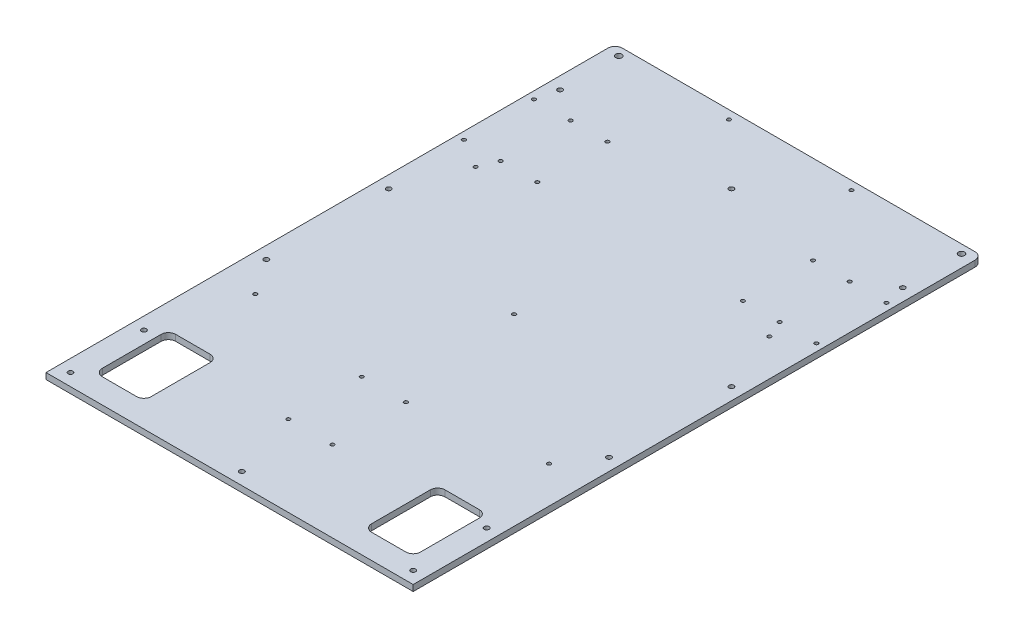
SolidWorks part; units mm, degrees
ref_plane "Front Plane" through (0, 0, 0) normal (0, 0, 1) x (1, 0, 0)
ref_plane "Top Plane" through (0, 0, 0) normal (0, 1, 0) x (1, 0, 0)
ref_plane "Right Plane" through (0, 0, 0) normal (1, 0, 0) x (0, 0, -1)
sketch "Sketch1" plane through (0, 0, 0) normal (0, 1, 0) x (1, 0, 0)
  line L0 (0, -210) -> (0, 210) construction
  line L1 (-150, -210) -> (150, -210)
  line L2 (-150, -210) -> (-150, 210)
  line L3 (-150, 210) -> (150, 210) construction
  line L4 (150, -210) -> (150, 210)
  line L5 (-150, 0) -> (150, 0) construction
  line L6 (-250, 154.9706) -> (0, 404.9706) construction
  line L7 (0, 404.9706) -> (250, 154.9706) construction
  line L8 (-130, -190) -> (-90, -190)
  line L9 (-130, -190) -> (-130, -130)
  line L10 (-130, -130) -> (-90, -130)
  line L11 (-90, -190) -> (-90, -130)
  line L12 (-130, -190) -> (-90, -130) construction
  line L13 (-130, -130) -> (-90, -190) construction
  line L14 (-250, 260) -> (250, 260) construction
  line L15 (-250, 260) -> (-250, -240) construction
  line L16 (-250, -240) -> (250, -240) construction
  line L17 (250, 260) -> (250, -240) construction
  line L18 (-188, 200) -> (-140, 200) construction
  line L19 (-165, 186) -> (-155, 186) construction
  line L20 (-165, 186) -> (-165, 122) construction
  line L21 (-165, 122) -> (-155, 122) construction
  line L22 (-155, 186) -> (-155, 122) construction
  line L23 (-140, 200) -> (-140, 248) construction
  line L24 (-140, 210) -> (-140, -210) construction
  line L25 (-150, -200) -> (150, -200) construction
  line L26 (-130, -160) -> (-90, -160) construction
  line L27 (-110, -190) -> (-110, -130) construction
  line L28 (-140, 248) -> (150, 248) construction
  line L29 (-140, 200) -> (0, 200) construction
  line L30 (0, 182.625) -> (-150, 182.625) construction
  line L31 (130, -190) -> (90, -190)
  line L32 (130, -190) -> (130, -130)
  line L33 (130, -130) -> (90, -130)
  line L34 (90, -190) -> (90, -130)
  line L35 (-200, -205) -> (-200, 200) construction
  line L36 (-155, 154) -> (0, 154) construction
  line L37 (-150, 190) -> (0, 190) construction
  line L38 (-150, 118) -> (0, 118) construction
  line L39 (-150, 210) -> (-150, 255)
  line L40 (-150, 255) -> (150, 255)
  line L41 (150, 255) -> (150, 210)
  circle A0 centre (-140, 248) radius 12 construction
  circle A1 centre (-188, 200) radius 12 construction
  circle A2 centre (-188, -205) radius 12 construction
  circle A3 centre (0, -200) radius 2
  circle A4 centre (-140, -200) radius 2
  circle A15 centre (-140, -40) radius 2
  circle A16 centre (-140, 60) radius 2
  circle A30 centre (140, -200) radius 2
  circle A31 centre (-114, 182.625) radius 1.5
  circle A32 centre (-144, 182.625) radius 1.5
  circle A33 centre (-84, 182.625) radius 1.5
  circle A34 centre (-84, 125.375) radius 1.5
  circle A35 centre (-114, 125.375) radius 1.5
  circle A36 centre (-144, 125.375) radius 1.5
  circle A37 centre (-140, -140) radius 2
  circle A38 centre (-140, 248) radius 2.5
  circle A39 centre (-50, 248) radius 1.5
  circle A40 centre (140, -140) radius 2
  circle A41 centre (140, -200) radius 2
  circle A42 centre (140, 60) radius 2
  circle A43 centre (140, -40) radius 2
  circle A44 centre (144, 125.375) radius 1.5
  circle A45 centre (114, 125.375) radius 1.5
  circle A46 centre (84, 125.375) radius 1.5
  circle A47 centre (84, 182.625) radius 1.5
  circle A48 centre (144, 182.625) radius 1.5
  circle A49 centre (114, 182.625) radius 1.5
  circle A51 centre (50, 248) radius 1.5
  circle A52 centre (140, 248) radius 2.5
  circle A53 centre (-140, 200) radius 2
  circle A54 centre (0, 200) radius 2
  circle A55 centre (140, 200) radius 2
  point P0 (0, 0)
  point P8 (-110, -160)
  point P17 (0, -240)
  dimension "D15" = 24
  dimension "D16" = 10
  dimension "D22" = 50
  dimension "D23" = 5
  dimension "D24" = 3
  dimension "D25" = 4
  dimension "D27" = 36
  dimension "D28" = 30
  dimension "D29" = 200
  dimension "D30" = 90
  dimension "D31" = 4
  dimension "D33" = 100
  dimension "D34" = 30
  dimension "D35" = 36
  dimension "D37" = 3
  dimension "D38" = 57.25
  dimension "D20" = 4
  dimension "D21" = 100
  dimension "D1" = 300
  dimension "D2" = 420
  dimension "D3" = 60
  dimension "D4" = 40
  dimension "D5" = 20
  dimension "D6" = 20
  dimension "D7" = 500
  dimension "D8" = 500
  dimension "D9" = 45
  dimension "D10" = 45
  dimension "D11" = 50
  dimension "D12" = 64
  dimension "D13" = 10
  dimension "D14" = 5
  dimension "D17" = 5
  dimension "D18" = 10
  dimension "D19" = 10
  dimension "D26" = 20
  dimension "D36" = 36
  dimension "D39" = 45
  dimension "D40" = 58
extrude "Boss-Extrude1" add sketch "Sketch1" along normal blind 5 contours L41 L40 L39 L2 L1 L4 A51 A48 A43 A40 A39 A38 A37 A35 A30 A16 A15 A4 A3 L11 L8 L9 L10 L31 L34 L33 L32 A31 region at (0, 0, -28.8924)
fillet "Fillet1" radius 6 10 edges at (-130, 2.5, 130) (150, 2.5, -255) (-150, 2.5, -255) (130, 2.5, 190) (130, 2.5, 130) (90, 2.5, 130) (90, 2.5, 190) (-130, 2.5, 190) (-90, 2.5, 190) (-90, 2.5, 130)
sketch "Sketch2" plane through (0, 5, 0) normal (0, 1, 0) x (1, 0, 0)
  line L0 (0, -210) -> (0, 255) construction
  line L1 (-150, -210) -> (150, -210) construction
  line L2 (-144, 255) -> (144, 255) construction
  line L8 (18, -84) -> (18, -144) construction
  line L9 (-24, -78) -> (24, -78) construction
  line L10 (-24, -78) -> (-24, -150) construction
  line L15 (-24, -150) -> (24, -150) construction
  line L16 (24, -78) -> (24, -150) construction
  line L17 (-24, -78) -> (24, -150) construction
  line L18 (-24, -150) -> (24, -78) construction
  line L19 (-18, -144) -> (18, -144) construction
  line L20 (-18, -84) -> (-18, -144) construction
  line L21 (-18, -84) -> (18, -84) construction
  line L31 (-120, 111) -> (120, 111) construction
  line L32 (-120, 111) -> (-120, -69) construction
  line L33 (-120, -69) -> (120, -69) construction
  line L34 (120, 111) -> (120, -69) construction
  line L35 (-120, 111) -> (120, -69) construction
  line L36 (-120, -69) -> (120, 111) construction
  circle A6 centre (-18, -144) radius 1.5
  circle A7 centre (18, -144) radius 1.5
  circle A8 centre (18, -84) radius 1.5
  circle A9 centre (-18, -84) radius 1.5
  circle A10 centre (-120, -69) radius 1.5
  circle A11 centre (120, -69) radius 1.5
  circle A12 centre (120, 111) radius 1.5
  circle A13 centre (-120, 111) radius 1.5
  circle A14 centre (0, 22.5) radius 1.5
  point P6 (0, -114)
  point P19 (0, 21)
  dimension "D5" = 60
  dimension "D7" = 180
  dimension "D4" = 3
  dimension "D1" = 48
  dimension "D2" = 72
  dimension "D3" = 6
  dimension "D6" = 240
  dimension "D8" = 21
extrude "Cut-Extrude1" cut sketch "Sketch2" against normal through all
